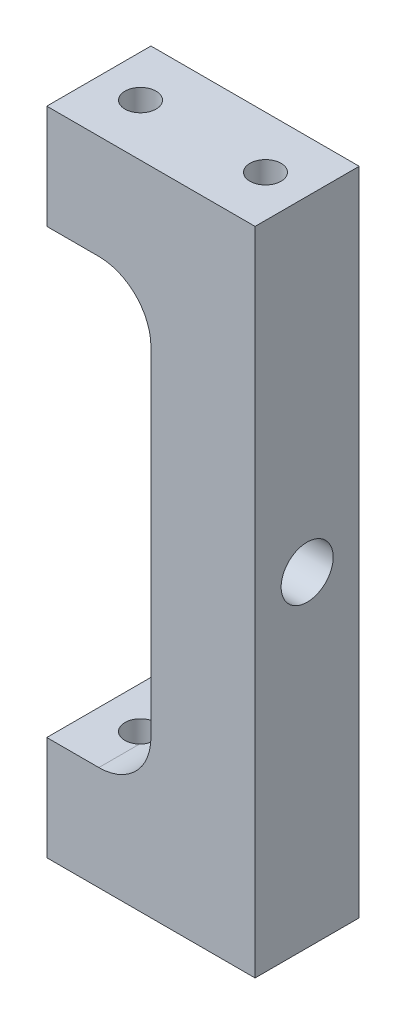
SolidWorks part; units mm, degrees
material "6061-T6 (SS)"
ref_plane "Front Plane" through (0, 0, 0) normal (0, 0, 1) x (1, 0, 0)
ref_plane "Top Plane" through (0, 0, 0) normal (0, 1, 0) x (1, 0, 0)
ref_plane "Right Plane" through (0, 0, 0) normal (1, 0, 0) x (0, 0, -1)
sketch "Sketch1" plane through (0, 0, 0) normal (0, 1, 0) x (1, 0, 0)
  line L1 (0, 0) -> (25.4, 0)
  line L2 (0, 0) -> (0, 12.7)
  line L3 (0, 12.7) -> (25.4, 12.7)
  line L4 (25.4, 0) -> (25.4, 12.7)
  line L5 (0, 0) -> (25.4, 12.7) construction
  line L6 (0, 12.7) -> (25.4, 0) construction
  point P4 (12.7, 6.35)
  dimension "D1" = 25.4
  dimension "D2" = 12.7
extrude "Stock" add sketch "Sketch1" along normal blind 79.375
sketch "Sketch2" plane through (0, 0, 0) normal (0, 0, 1) x (1, 0, 0)
  line L0 (0, 79.375) -> (0, 0) construction
  line L1 (0, 66.675) -> (12.7, 66.675)
  line L2 (0, 66.675) -> (0, 12.7)
  line L3 (0, 12.7) -> (12.7, 12.7)
  line L4 (12.7, 66.675) -> (12.7, 12.7)
  line L5 (0, 66.675) -> (12.7, 12.7) construction
  line L6 (0, 12.7) -> (12.7, 66.675) construction
  line L7 (25.4, 39.6875) -> (0, 39.6875) construction
  line L8 (25.4, 79.375) -> (25.4, 0) construction
  line L9 (0, 79.375) -> (25.4, 79.375) construction
  point P4 (6.35, 39.6875)
  dimension "D1" = 12.7
  dimension "D2" = 12.7
extrude "Cutout" cut sketch "Sketch2" against normal through all
fillet "Fillet1" radius 6.35 2 edges at (12.7, 12.7, -6.35) (12.7, 66.675, -6.35)
sketch "Spring Bolt Hole Position" plane through (12.7, 0, 0) normal (-1, 0, 0) x (0, 0, 1)
  line L0 (-12.7, 39.6875) -> (0, 39.6875) construction
  line L1 (-12.7, 19.05) -> (-12.7, 60.325) construction
  line L2 (0, 19.05) -> (0, 60.325) construction
  line L3 (-6.35, 79.375) -> (-6.35, 0) construction
  line L4 (-12.7, 79.375) -> (0, 79.375) construction
  line L5 (-12.7, 0) -> (0, 0) construction
  point P12 (-6.35, 39.6875)
hole_wizard "1/4 (0.25) Diameter Hole1" positions "Sketch4" profile "Sketch5" hole size "1/4" standard "ANSI Inch" end condition through all
sketch "Sketch4" plane through (12.7, 0, 0) normal (-1, 0, 0) x (0, 0, 1)
  point P0 (-6.35, 39.6875)
sketch "Sketch5" plane through (12.7, 39.6875, -6.35) normal (0, 1, 0) x (0, 0, 1)
  line L0 (0, 0) -> (0, 12.7)
  line L1 (0, 12.7) -> (3.175, 12.7)
  line L2 (3.175, 12.7) -> (3.175, 0)
  line L5 (3.175, 0) -> (0, 0)
  line L11 (0, -6.35) -> (0, 107.95) construction
  dimension "Thru Hole Dia." = 6.35
  dimension "Thru Hole Depth" = 12.7
sketch "Mounting Hole Positions" plane through (0, 79.375, 0) normal (0, 1, 0) x (1, 0, 0)
  line L0 (0, 6.35) -> (25.4, 6.35) construction
  line L1 (0, 12.7) -> (0, 0) construction
  line L2 (25.4, 0) -> (25.4, 12.7) construction
  line L3 (12.7, 12.7) -> (12.7, 0) construction
  line L4 (25.4, 12.7) -> (0, 12.7) construction
  point P6 (5.08, 6.35)
  point P7 (20.32, 6.35)
  dimension "D1" = 5.08
hole_wizard "Mounting Holes One Side" positions "Sketch7" profile "Sketch8" tap size "#10-24" standard "ANSI Inch"
sketch "Sketch7" plane through (0, 79.375, 0) normal (0, 1, 0) x (1, 0, 0)
  point P0 (5.08, 6.35)
  point P3 (20.32, 6.35)
sketch "Sketch8" plane through (5.08, 79.375, -6.35) normal (1, 0, 0) x (0, 0, 1)
  line L0 (0, 0) -> (0, 13.8408)
  line L1 (0, 13.8408) -> (1.8986, 12.7)
  line L2 (1.8986, 12.7) -> (1.8986, 0)
  line L5 (1.8986, 0) -> (0, 0)
  line L10 (0, 13.8408) -> (-1.8987, 12.7) construction
  line L11 (0, -6.35) -> (0, 107.95) construction
  dimension "Tap Drill Dia." = 3.7973
  dimension "Tap Drill Depth" = 12.7
  dimension "Drill Angle" = 118
cosmetic thread "Hole Thread1" parameters "D1"=9.652, "D2"=4.826
cosmetic thread "Hole Thread2" parameters "D1"=9.652, "D2"=4.826
ref_plane "Middle Plane" through (0, 39.6875, 0) normal (0, -1, 0) x (-1, 0, 0)
mirror "Mounting Holes" about plane through (0, 39.6875, 0) normal (0, -1, 0) of "Mounting Holes One Side"
